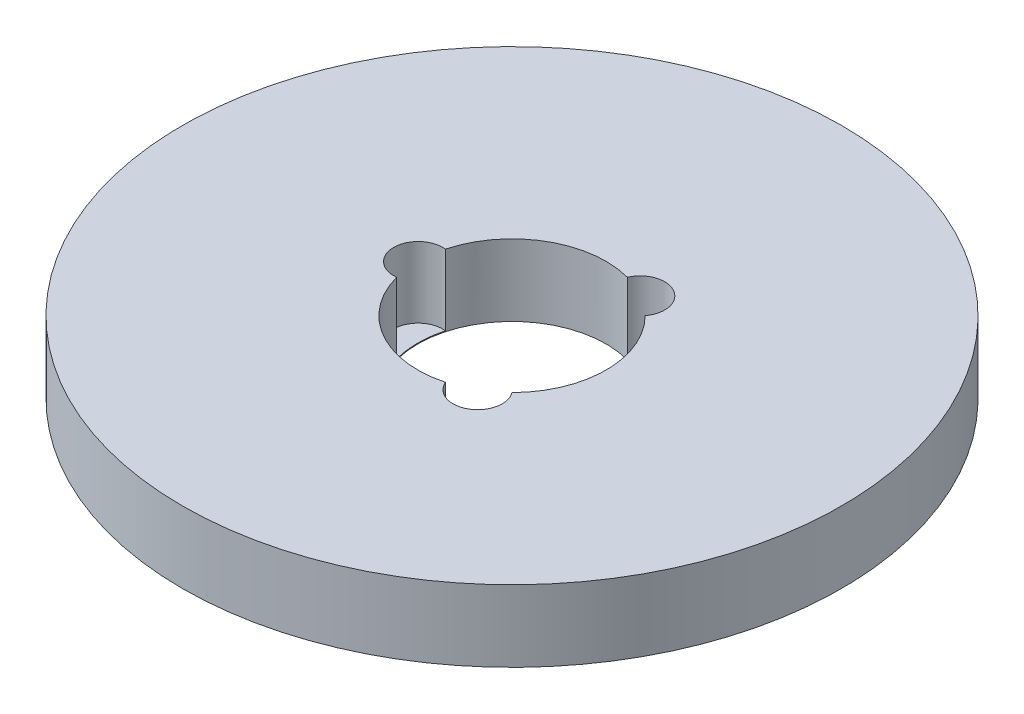
SolidWorks part; units mm, degrees
ref_plane "Front Plane" through (0, 0, 0) normal (0, 0, 1) x (1, 0, 0)
ref_plane "Top Plane" through (0, 0, 0) normal (0, 1, 0) x (1, 0, 0)
ref_plane "Right Plane" through (0, 0, 0) normal (1, 0, 0) x (0, 0, -1)
sketch "Sketch1" plane through (0, 0, 0) normal (0, 1, 0) x (1, 0, 0)
  circle A0 centre (0, 0) radius 87.5
  dimension "FLANGE_OD" = 175
extrude "Boss-Extrude1" add sketch "Sketch1" along normal blind 19
sketch "Sketch2" plane through (0, 0, 0) normal (0, 1, 0) x (1, 0, 0)
  circle A0 centre (0, 0) radius 25
  dimension "BORE_D" = 50
extrude "Cut-Extrude1" cut sketch "Sketch2" along normal through all
sketch "Sketch3" plane through (0, 19, 0) normal (0, 1, 0) x (1, 0, 0)
  circle A0 centre (0, 0) radius 24.9106 construction
  circle A1 centre (-24.9106, 0) radius 6.5127
  dimension "BOLT_D" = 13.0254
  dimension "BOLT_PCD" = 49.8213
extrude "Cut-Extrude2" cut sketch "Sketch3" against normal blind 18.7707
pattern_circular "CirPattern1" count 3 over 360 about axis through (0, 0, 0) along (0, 1, 0) of "Cut-Extrude2"
